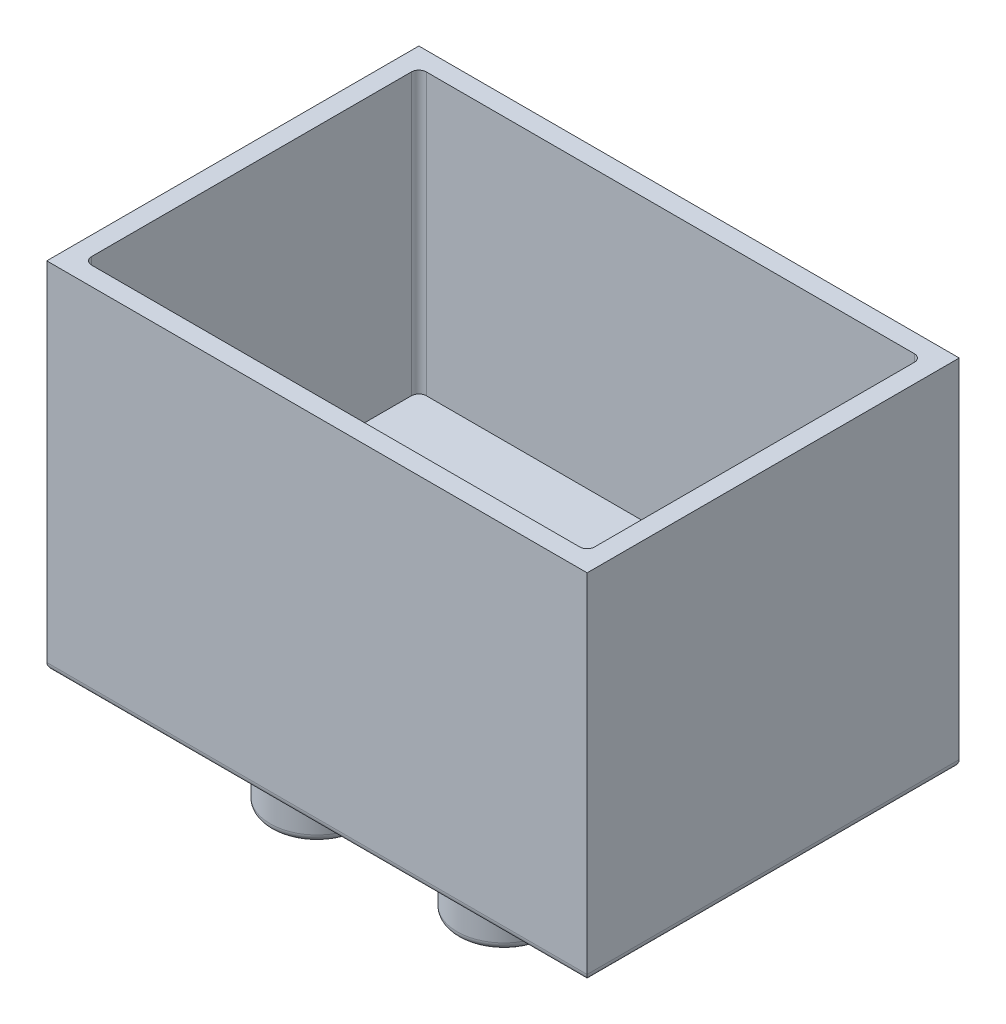
SolidWorks part; units mm, degrees
ref_plane "Front Plane" through (0, 0, 0) normal (0, 0, 1) x (1, 0, 0)
ref_plane "Top Plane" through (0, 0, 0) normal (0, 1, 0) x (1, 0, 0)
ref_plane "Right Plane" through (0, 0, 0) normal (1, 0, 0) x (0, 0, -1)
sketch "Sketch1" plane through (0, 0, 0) normal (0, 1, 0) x (1, 0, 0)
  line L0 (-0.2, 17.7) -> (26.7, 17.7)
  line L1 (0, 0) -> (26.5, 0)
  line L2 (0, 0) -> (0, 17.5)
  line L3 (0, 17.5) -> (26.5, 17.5)
  line L4 (26.5, 0) -> (26.5, 17.5)
  line L5 (26.7, -0.2) -> (26.7, 17.7)
  line L6 (-0.2, -0.2) -> (26.7, -0.2)
  line L7 (-0.2, -0.2) -> (-0.2, 17.7)
  line L8 (-1.2, 18.7) -> (27.7, 18.7)
  line L9 (27.7, -1.2) -> (27.7, 18.7)
  line L10 (-1.2, -1.2) -> (27.7, -1.2)
  line L11 (-1.2, -1.2) -> (-1.2, 18.7)
  dimension "D1" = 17.5
  dimension "D2" = 26.5
  dimension "D3" = 0.2
  dimension "D4" = 1
extrude "Boss-Extrude1" add sketch "Sketch1" along normal blind 15 contours L11 L10 L9 L8 L6 L7 L0 L5 region at (13.25, 0, -18.3491)
extrude "Boss-Extrude2" add sketch "Sketch1<3>" against normal blind 4 contours L11 L10 L9 L8 L6 L7 L0 L5 | L1 L4 L3 L2 | L7 L6 L5 L0 L4 L1 L2 L3 region at (13.25, 0, -17.6677) region at (13.25, 0, -8.75) region at (13.25, 0, -18.3491)
sketch "Sketch1<3>" plane through (0, 0, 0) normal (0, 1, 0) x (1, 0, 0) same geometry as "Sketch1"
sketch "Sketch2" plane through (0, -4, 0) normal (0, -1, 0) x (1, 0, 0)
  line L0 (13.25, 1.2) -> (13.25, -18.7) construction
  line L1 (-1.2, 1.2) -> (27.7, 1.2) construction
  line L2 (-1.2, -18.7) -> (27.7, -18.7) construction
  line L3 (-1.2, -3.8) -> (27.7, -3.8) construction
  line L4 (-1.2, 1.2) -> (-1.2, -18.7) construction
  line L5 (27.7, 1.2) -> (27.7, -18.7) construction
  circle A0 centre (8.25, -3.8) radius 2.5
  circle A1 centre (18.25, -3.8) radius 2.5
  dimension "D2" = 5
  dimension "D1" = 5
  dimension "D3" = 5
extrude "Boss-Extrude3" add sketch "Sketch2" along normal blind 4
fillet "Fillet1" radius 0.4 8 edges at (13.25, -4, 1.2) (27.7, -4, -8.75) (13.25, -4, -18.7) (-1.2, -4, -8.75) (8.25, -4, -1.3) (18.25, -4, -1.3) (18.25, -8, -1.3) (8.25, -8, -6.3)
fillet "Fillet2" radius 0.4 4 edges at (26.7, 7.5, 0.2) (26.7, 7.5, -17.7) (-0.2, 7.5, 0.2) (-0.2, 7.5, -17.7)
